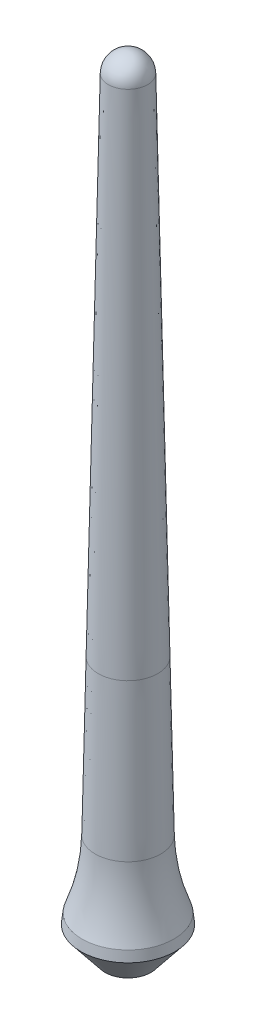
SolidWorks part; units mm, degrees
ref_plane "Front Plane" through (0, 0, 0) normal (0, 0, 1) x (1, 0, 0)
ref_plane "Top Plane" through (0, 0, 0) normal (0, 1, 0) x (1, 0, 0)
ref_plane "Right Plane" through (0, 0, 0) normal (1, 0, 0) x (0, 0, -1)
sketch "Sketch1" plane through (0, 0, 0) normal (0, 0, 1) x (1, 0, 0)
  line L0 (0, 0) -> (0, 120)
  line L1 (3, 117.059) -> (5, 16.4072)
  line L2 (7.5, 5) -> (3.5, 0)
  line L3 (3.5, 0) -> (0, 0)
  line L4 (0, 0) -> (0, -29.0188) construction
  arc A0 (0, 120) -> (3, 117.059) centre (0, 116.9994) cw
  arc A1 (5, 16.4072) -> (7.5, 5) centre (34.9941, 17.0031) ccw
  point P8 (9.0242, 24.0871)
  point P10 (15, 10.3676)
  point P11 (6.6248, 25.708)
  point P12 (10.1756, 20.3843)
  point P13 (12.5, 10.5646)
  dimension "D2" = 6
  dimension "D3" = 30
  dimension "D1" = 120
  dimension "D4" = 15
  dimension "D5" = 7
  dimension "D6" = 10
  dimension "D7" = 5
revolve "Revolve1" add sketch "Sketch1" angle 360 about L4
sketch "Sketch2" plane through (0, 0, 0) normal (0, -1, 0) x (1, 0, 0)
  circle A0 centre (0, 0) radius 2
  dimension "D1" = 4
extrude "Cut-Extrude1" cut sketch "Sketch2" against normal blind 10
chamfer "Chamfer1" distance 0.5 angle 45 1 edges at (0, 5, 7.5) first distance on face at (0, 5, 7.5)
ref_plane "Plane1" through (0, 40, 0) normal (0, 1, 0) x (1, 0, 0)
split "Split1" trim tools "Plane1" bodies to split 102 resulting bodies 103 104
